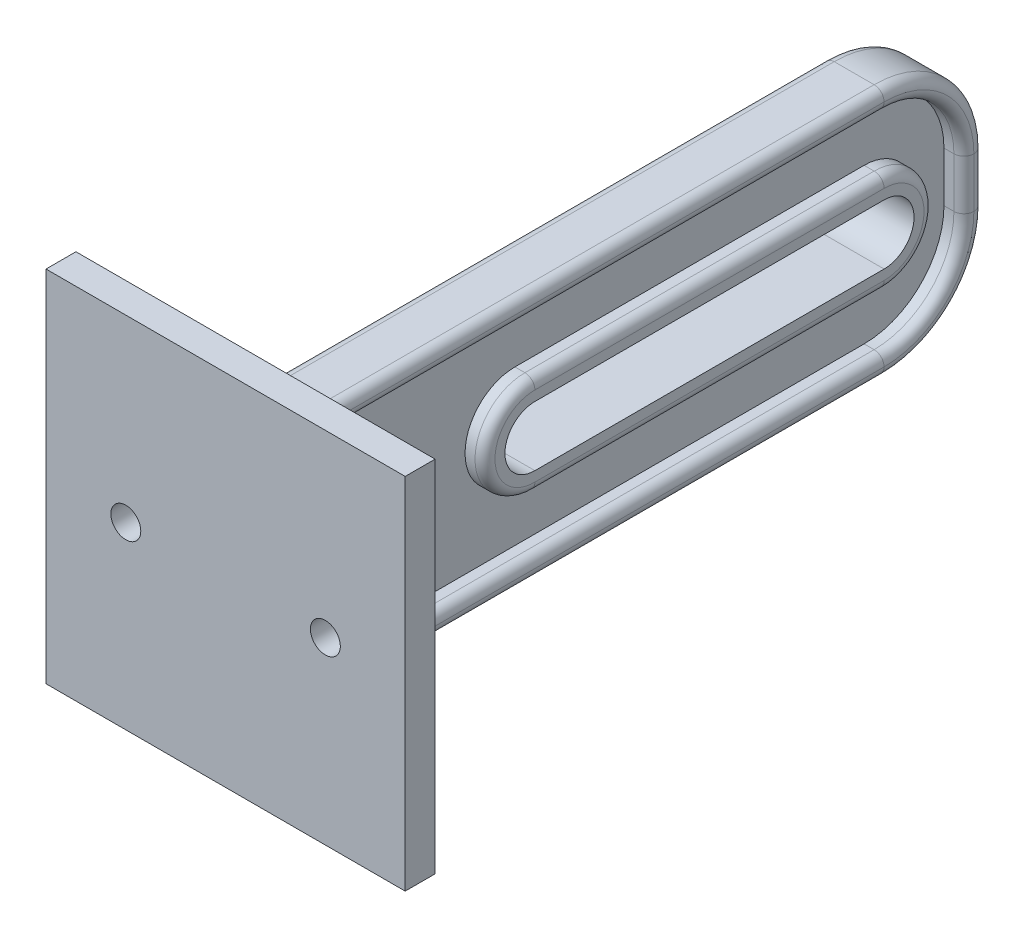
SolidWorks part; units mm, degrees
ref_plane "Front Plane" through (0, 0, 0) normal (0, 0, 1) x (1, 0, 0)
ref_plane "Top Plane" through (0, 0, 0) normal (0, 1, 0) x (1, 0, 0)
ref_plane "Right Plane" through (0, 0, 0) normal (1, 0, 0) x (0, 0, -1)
sketch "Sketch1" plane through (0, 0, 0) normal (0, 0, 1) x (1, 0, 0)
  line L1 (-18, 18) -> (18, 18)
  line L2 (-18, 18) -> (-18, -18)
  line L3 (-18, -18) -> (18, -18)
  line L4 (18, 18) -> (18, -18)
  line L5 (-18, 18) -> (18, -18) construction
  line L6 (-18, -18) -> (18, 18) construction
  point P0 (0, 0)
  dimension "D1" = 36
  dimension "D2" = 36
extrude "Boss-Extrude1" add sketch "Sketch1" along normal blind 3
sketch "Sketch2" plane through (0, 0, 3) normal (0, 0, 1) x (1, 0, 0)
  line L0 (-18, 0) -> (18, 0) construction
  line L1 (-18, 18) -> (-18, -18) construction
  line L2 (18, -18) -> (18, 18) construction
  line L3 (0, 0) -> (0, 18) construction
  line L4 (18, 18) -> (-18, 18) construction
  circle A0 centre (-10, 0) radius 1.5
  circle A1 centre (10, 0) radius 1.5
  dimension "D1" = 3
  dimension "D3" = 20
extrude "Cut-Extrude1" cut sketch "Sketch2" against normal through all
sketch "Sketch3" plane through (0, 0, 0) normal (0, 0, -1) x (-1, 0, 0)
  line L1 (3, 12.5) -> (-3, 12.5)
  line L2 (3, 12.5) -> (3, -12.5)
  line L3 (3, -12.5) -> (-3, -12.5)
  line L4 (-3, 12.5) -> (-3, -12.5)
  line L5 (3, 12.5) -> (-3, -12.5) construction
  line L6 (3, -12.5) -> (-3, 12.5) construction
  point P0 (0, 0)
  dimension "D1" = 25
  dimension "D2" = 6
extrude "Boss-Extrude2" add sketch "Sketch3" along normal blind 70 contours L2 L1 L4 L3
fillet "Fillet1" radius 10 2 edges at (0, 12.5, -70) (0, -12.5, -70)
sketch "Sketch4" plane through (-3, 0, 0) normal (-1, 0, 0) x (0, 0, 1)
  line L0 (0, 0) -> (-70, 0) construction
  line L1 (-70, 2.5) -> (-70, -2.5) construction
  line L2 (-60, -3) -> (-25, -3)
  line L3 (-60, 3) -> (-25, 3)
  arc A0 (-60, -3) -> (-60, 3) centre (-60, 0) cw
  arc A1 (-25, -3) -> (-25, 3) centre (-25, 0) ccw
  dimension "D1" = 3
  dimension "D2" = 10
  dimension "D3" = 35
  dimension "D4" = 35
extrude "Cut-Extrude2" cut sketch "Sketch4" against normal through all
sketch "Sketch6" plane through (-3, 0, 0) normal (-1, 0, 0) x (0, 0, 1)
  line L17 (-2, -10.5) -> (-2, 10.5)
  line L18 (-2, 10.5) -> (-60, 10.5)
  line L19 (-68, 2.5) -> (-68, -2.5)
  line L20 (-60, -10.5) -> (-2, -10.5)
  line L21 (-2, -10.5) -> (-2, 10.5)
  line L22 (-2, 10.5) -> (-60, 10.5)
  line L23 (-68, 2.5) -> (-68, -2.5)
  line L24 (-60, -10.5) -> (-2, -10.5)
  line L28 (-60, -5) -> (-25, -5)
  line L29 (-25, 5) -> (-60, 5)
  line L30 (-60, -5) -> (-25, -5)
  line L31 (-25, 5) -> (-60, 5)
  arc A10 (-60, 10.5) -> (-68, 2.5) centre (-60, 2.5) ccw
  arc A11 (-68, -2.5) -> (-60, -10.5) centre (-60, -2.5) ccw
  arc A12 (-60, 10.5) -> (-68, 2.5) centre (-60, 2.5) ccw
  arc A13 (-68, -2.5) -> (-60, -10.5) centre (-60, -2.5) ccw
  arc A19 (-25, -5) -> (-25, 5) centre (-25, 0) ccw
  arc A20 (-60, 5) -> (-60, -5) centre (-60, 0) ccw
  arc A21 (-25, -5) -> (-25, 5) centre (-25, 0) ccw
  arc A22 (-60, 5) -> (-60, -5) centre (-60, 0) ccw
  dimension "D1" = 2
  dimension "D2" = 2
extrude "Cut-Extrude3" cut sketch "Sketch6" against normal blind 2
mirror "Mirror1" about plane through (0, 0, 0) normal (1, 0, 0) of "Cut-Extrude3"
fillet "Fillet2" radius 1 35 edges at (-3, 0, 0) (0, 12.5, 0) (0, -12.5, 0) (-1, -5, -42.5) (-1, 0, -65) (-1, 5, -42.5) (-3, 12.5, -30) (-3, -12.5, -30) (-3, -9.5711, -67.0711) (-3, 0, -70) (-3, 10.5, -31) (-3, 8.1569, -65.6569) (-3, 0, -68) (-3, -10.5, -31) (3, 12.5, -30) (3, 9.5711, -67.0711) (3, 0, -70) (3, -9.5711, -67.0711) (3, 0, -20) (3, -5, -42.5) (3, 0, -65) (3, -10.5, -31) (3, -8.1569, -65.6569) (3, 0, -68) (3, 8.1569, -65.6569) (-1, 0, -2) (-1, 0, -20) (-3, 9.5711, -67.0711) (-3, -8.1569, -65.6569) (3, -12.5, -30) (3, 0, 0) (3, 0, -2) (1, 0, -2) (3, 5, -42.5) (3, 10.5, -31)
